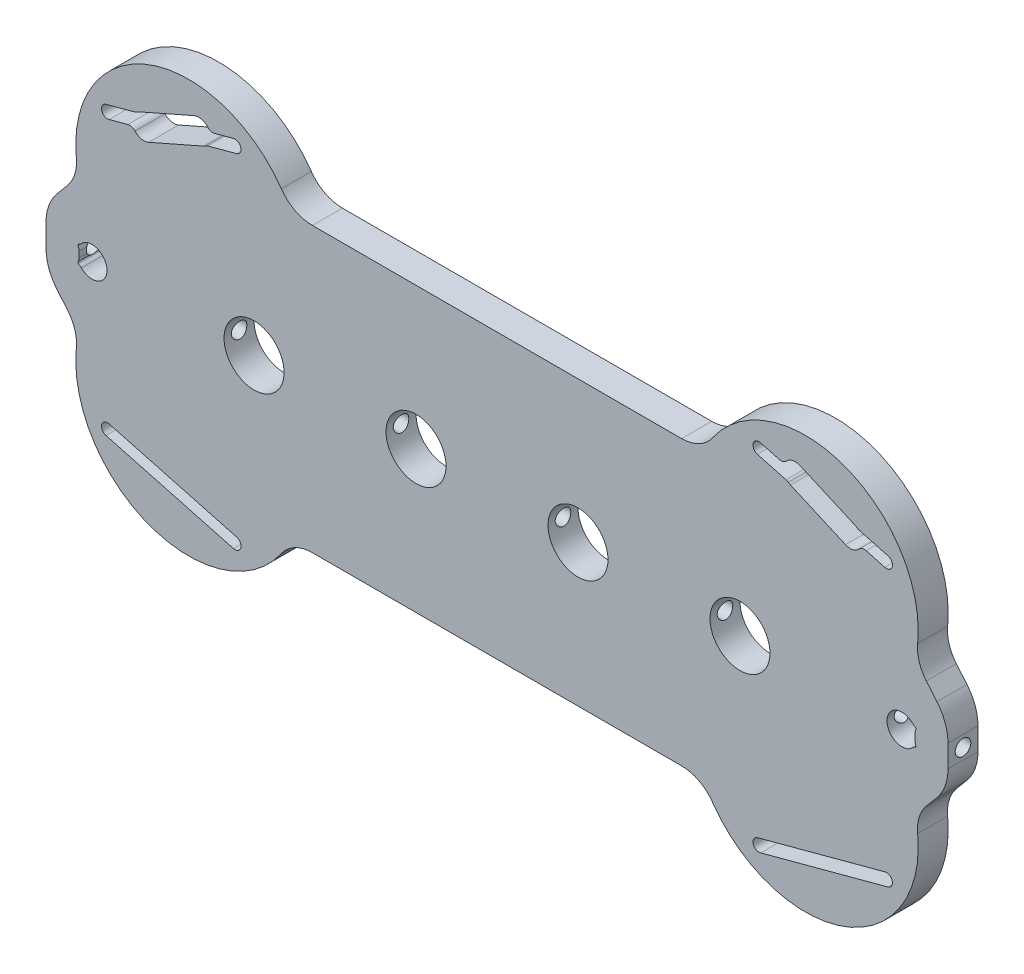
SolidWorks part; units mm, degrees
ref_plane "Front Plane" through (0, 0, 0) normal (0, 0, 1) x (1, 0, 0)
ref_plane "Top Plane" through (0, 0, 0) normal (0, 1, 0) x (1, 0, 0)
ref_plane "Right Plane" through (0, 0, 0) normal (1, 0, 0) x (0, 0, -1)
sketch "Sketch1" plane through (0, 0, 0) normal (0, 0, 1) x (1, 0, 0)
  line L0 (-85.725, 0) -> (85.725, 0) construction
  line L1 (-85.725, 30) -> (85.725, 30)
  line L2 (-85.725, -30) -> (85.725, -30)
  line L3 (0, 30) -> (0, -30) construction
  line L4 (-75.3362, 30) -> (-95.4746, 6)
  line L5 (-95.4746, 6) -> (-95.4746, -6)
  line L6 (-95.4746, -6) -> (-75.3362, -30)
  line L7 (-88.4746, -0.7777) -> (-88.4746, -1.5875) construction
  line L8 (-88.4746, -0.7777) -> (-88.4746, 0.7777) construction
  line L9 (-88.4746, 1.5875) -> (-88.4746, 0.7777) construction
  line L13 (88.4746, 1.3375) -> (88.4746, -1.3375)
  line L14 (-88.4746, 1.3375) -> (-88.4746, -1.3375)
  line L15 (95.4746, -6) -> (75.3362, -30)
  line L16 (95.4746, 6) -> (95.4746, -6)
  line L17 (75.3362, 30) -> (95.4746, 6)
  arc A0 (-85.725, 30) -> (-85.725, -30) centre (-85.725, 0) ccw
  arc A1 (85.725, -30) -> (85.725, 30) centre (85.725, 0) ccw
  arc A5 (-88.4746, -1.5875) -> (-88.4746, 1.5875) centre (-85.725, 0) ccw construction
  circle A6 centre (-88.4746, 1.5875) radius 0.25 construction
  circle A7 centre (-88.4746, -1.5875) radius 0.25 construction
  arc A11 (88.4746, -1.3375) -> (88.3412, -1.7989) centre (88.4746, -1.5875) cw
  arc A12 (88.3412, 1.7989) -> (88.4746, 1.3375) centre (88.4746, 1.5875) cw
  arc A13 (88.3412, 1.7989) -> (88.3412, -1.7989) centre (85.725, 0) ccw
  arc A14 (-88.3412, 1.7989) -> (-88.3412, -1.7989) centre (-85.725, 0) cw
  arc A15 (-88.3412, 1.7989) -> (-88.4746, 1.3375) centre (-88.4746, 1.5875) ccw
  arc A16 (-88.3412, -1.7989) -> (-88.4746, -1.3375) centre (-88.4746, -1.5875) cw
  circle A17 centre (51.435, 0) radius 6.35
  circle A18 centre (17.145, 0) radius 6.35
  circle A19 centre (-17.145, 0) radius 6.35
  circle A20 centre (-51.435, 0) radius 6.35
  point P3 (0, 0)
  point P37 (51.435, 0)
  point P38 (-95.4746, 0)
  point P39 (85.725, 0)
  point P40 (17.145, 0)
  point P41 (-17.145, 0)
  point P46 (-51.435, 0)
  dimension "D2" = 0.5
  dimension "D4" = 0.5
  dimension "D9" = 12.7
  dimension "D1" = 171.45
  dimension "D3" = 60
  dimension "D5" = 7
  dimension "D6" = 220
  dimension "D7" = 12
  dimension "D8" = 5
extrude "Boss-Extrude1" add sketch "Sketch1" along normal mid plane 6.35 contours L2 A1 L1 A0 L4 L5 L6 A13 A12 L13 A11 A14 A16 L14 A15 region at (0, 0, 0)
fillet "Fillet1" radius 2 8 edges at (-88.3412, 1.7989, 0) (88.3412, -1.7989, 0) (88.4746, -1.3375, 0) (88.4746, 1.3375, 0) (88.3412, 1.7989, 0) (-88.3412, -1.7989, 0) (-88.4746, -1.3375, 0) (-88.4746, 1.3375, 0)
fillet "Fillet2" radius 10 4 edges at (-95.4746, -6, 0) (-95.4746, 6, 0) (95.4746, -6, 0) (95.4746, 6, 0)
fillet "Fillet3" radius 20 4 edges at (-75.3362, 30, 0) (-75.3362, -30, 0) (75.3362, -30, 0) (75.3362, 30, 0)
hole_wizard "M4x0.7 Tapped Hole1" positions "Sketch3" profile "Sketch4" tap size "M4x0.7" standard "ANSI Metric" end condition through all
sketch "Sketch3" plane through (-95.4746, 0, 0) normal (-1, 0, 0) x (0, 0, 1)
  point P0 (0, 0)
cosmetic thread "Hole Thread1" parameters "D2"=4
sketch "Sketch4" plane through (-95.4746, 0, 0) normal (0, 1, 0) x (0, 0, 1)
  line L0 (0, 0) -> (0, 190.9493)
  line L1 (0, 190.9493) -> (1.65, 190.9493)
  line L2 (1.65, 190.9493) -> (1.65, 0)
  line L5 (1.65, 0) -> (0, 0)
  line L11 (0, -6.35) -> (0, 107.95) construction
  dimension "Thru Tap Drill Dia." = 3.3
  dimension "Thru Tap Drill Depth" = 190.9493
sketch "Sketch5" plane through (0, 0, 0) normal (0, 0, 1) x (1, 0, 0)
  line L0 (0, 30) -> (0, -30) construction
  line L1 (-66.0101, 30) -> (66.0101, 30) construction
  line L2 (-66.0101, -30) -> (66.0101, -30) construction
  line L3 (95.4746, 0) -> (-95.4746, 0) construction
  line L4 (-75.7735, 32.482) -> (-64.1475, 37.5933) construction
  line L5 (-81.331, 22.8558) -> (-93.1351, 8.7882) construction
  line L6 (-69.9605, 35.0376) -> (-67.9482, 30.4604) construction
  line L7 (-73.7612, 27.9048) -> (-62.1351, 33.0161) construction
  line L8 (-73.7612, 27.9048) -> (-62.1351, 33.0161)
  line L9 (-75.7735, 32.482) -> (-64.1475, 37.5933)
  line L10 (-43.666, 30) -> (-88.525, 14.2822)
  line L11 (69.9605, 35.0376) -> (67.9482, 30.4604) construction
  line L12 (43.666, 30) -> (88.525, 14.2822)
  line L13 (75.7735, 32.482) -> (64.1475, 37.5933)
  line L14 (73.7612, 27.9048) -> (62.1351, 33.0161)
  line L15 (95.4746, 2.3603) -> (95.4746, -2.3603) construction
  line L16 (-95.4746, 2.3603) -> (-95.4746, -2.3603) construction
  line L17 (-43.666, -30) -> (-88.525, -14.2822)
  line L18 (43.666, -30) -> (88.525, -14.2822)
  arc A0 (-43.666, 30) -> (-88.525, 14.2822) centre (-65.279, 19.8108) ccw
  arc A1 (-62.1351, 33.0161) -> (-64.1475, 37.5933) centre (-63.1413, 35.3047) ccw construction
  arc A2 (-75.7735, 32.482) -> (-73.7612, 27.9048) centre (-74.7673, 30.1934) ccw construction
  arc A3 (-75.7735, 32.482) -> (-73.7612, 27.9048) centre (-74.7673, 30.1934) ccw
  arc A4 (-62.1351, 33.0161) -> (-64.1475, 37.5933) centre (-63.1413, 35.3047) ccw
  arc A5 (62.1351, 33.0161) -> (64.1475, 37.5933) centre (63.1413, 35.3047) cw
  arc A6 (75.7735, 32.482) -> (73.7612, 27.9048) centre (74.7673, 30.1934) cw
  arc A7 (43.666, 30) -> (88.525, 14.2822) centre (65.279, 19.8108) cw
  arc A8 (-43.666, -30) -> (-88.525, -14.2822) centre (-65.279, -19.8108) cw
  arc A9 (43.666, -30) -> (88.525, -14.2822) centre (65.279, -19.8108) ccw
  point P10 (-73.1802, 42.3611)
  point P24 (-60.8527, 36.3108)
  point P32 (73.1802, 42.3611)
  dimension "D2" = 16.5
  dimension "D1" = 8
extrude "Boss-Extrude2" add sketch "Sketch5" along normal mid plane 6.35
fillet "Fillet4" radius 8 8 edges at (-88.525, 14.2822, 0) (-43.666, 30, 0) (43.666, 30, 0) (88.525, 14.2822, 0) (-88.525, -14.2822, 0) (-43.666, -30, 0) (43.666, -30, 0) (88.525, -14.2822, 0)
sketch "Sketch6" plane through (0, 0, 0) normal (0, 0, 1) x (1, 0, 0)
  line L0 (0, 30) -> (0, -30) construction
  line L1 (-39.0796, 30) -> (39.0796, 30) construction
  line L2 (-39.0796, -30) -> (39.0796, -30) construction
  line L3 (95.4746, 0) -> (-95.4746, 0) construction
  line L4 (-95.4746, 2.3603) -> (-95.4746, -2.3603) construction
  line L5 (95.4746, 2.3603) -> (95.4746, -2.3603) construction
  line L6 (-55.4603, 36.3647) -> (-82.4483, 29.1333) construction
  line L9 (-73.7612, 27.9048) -> (-62.1351, 33.0161) construction
  line L10 (-55.1316, 35.138) -> (-82.1196, 27.9066)
  line L11 (-64.1475, 37.5933) -> (-75.7735, 32.482) construction
  line L12 (-55.789, 37.5915) -> (-82.777, 30.3601)
  line L13 (-69.9605, 35.0376) -> (-67.9482, 30.4604) construction
  line L15 (-73.7612, 27.9048) -> (-62.1351, 33.0161)
  line L16 (-64.1475, 37.5933) -> (-75.7735, 32.482)
  line L17 (55.4603, 36.3647) -> (82.4483, 29.1333) construction
  line L18 (55.1316, 35.138) -> (82.1196, 27.9066)
  line L19 (55.789, 37.5915) -> (82.777, 30.3601)
  line L20 (64.1475, 37.5933) -> (75.7735, 32.482)
  line L21 (73.7612, 27.9048) -> (62.1351, 33.0161)
  line L22 (55.4603, -36.3647) -> (82.4483, -29.1333) construction
  line L23 (55.1316, -35.138) -> (82.1196, -27.9066)
  line L24 (55.789, -37.5915) -> (82.777, -30.3601)
  line L25 (-55.4603, -36.3647) -> (-82.4483, -29.1333) construction
  line L26 (-55.1316, -35.138) -> (-82.1196, -27.9066)
  line L27 (-55.789, -37.5915) -> (-82.777, -30.3601)
  arc A2 (-55.1316, 35.138) -> (-55.789, 37.5915) centre (-55.4603, 36.3647) ccw
  arc A3 (-82.777, 30.3601) -> (-82.1196, 27.9066) centre (-82.4483, 29.1333) ccw
  arc A4 (-75.7735, 32.482) -> (-73.7612, 27.9048) centre (-74.7673, 30.1934) ccw construction
  arc A5 (-62.1351, 33.0161) -> (-64.1475, 37.5933) centre (-63.1413, 35.3047) ccw construction
  arc A6 (-75.7735, 32.482) -> (-73.7612, 27.9048) centre (-74.7673, 30.1934) ccw
  arc A7 (-62.1351, 33.0161) -> (-64.1475, 37.5933) centre (-63.1413, 35.3047) ccw
  arc A8 (55.1316, 35.138) -> (55.789, 37.5915) centre (55.4603, 36.3647) cw
  arc A9 (82.777, 30.3601) -> (82.1196, 27.9066) centre (82.4483, 29.1333) cw
  arc A10 (62.1351, 33.0161) -> (64.1475, 37.5933) centre (63.1413, 35.3047) cw
  arc A11 (75.7735, 32.482) -> (73.7612, 27.9048) centre (74.7673, 30.1934) cw
  arc A12 (55.1316, -35.138) -> (55.789, -37.5915) centre (55.4603, -36.3647) ccw
  arc A13 (82.777, -30.3601) -> (82.1196, -27.9066) centre (82.4483, -29.1333) ccw
  arc A14 (-55.1316, -35.138) -> (-55.789, -37.5915) centre (-55.4603, -36.3647) cw
  arc A15 (-82.777, -30.3601) -> (-82.1196, -27.9066) centre (-82.4483, -29.1333) cw
  point P14 (-68.9543, 32.749)
  point P32 (68.9543, 32.749)
  point P45 (68.9543, -32.749)
  point P52 (-68.9543, -32.749)
  dimension "D1" = 15
  dimension "D2" = 27.94
  dimension "D3" = 2.54
extrude "Cut-Extrude1" cut sketch "Sketch6" against normal through all both and the other way through all contours L15 A7 L10 A6 | L19 A9 L18 A8 | L12 A3 L10 A2 | L15 A7 L16 A6 | L21 A10 L20 A11 | L23 A13 L24 A12 | L27 A15 L26 A14 region at (-71.0211, 30.0721, 0)
fillet "Fillet5" radius 1.5 8 edges at (-60.8238, 36.2424, 0) (-76.4294, 32.0609, 0) (-77.0848, 29.2557, 0) (-61.4793, 33.4372, 0) (61.4793, 33.4372, 0) (60.8238, 36.2424, 0) (76.4294, 32.0609, 0) (77.0848, 29.2557, 0)
